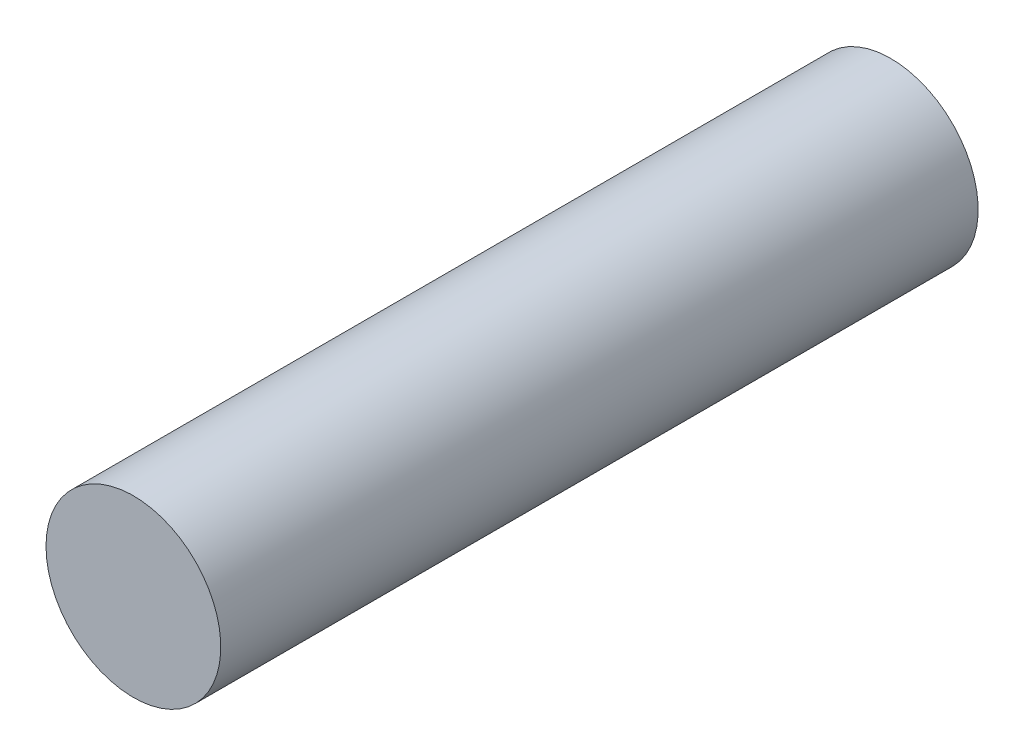
SolidWorks part; units mm, degrees
ref_plane "Front" through (0, 0, 0) normal (0, 0, 1) x (1, 0, 0)
ref_plane "Top" through (0, 0, 0) normal (0, 1, 0) x (1, 0, 0)
ref_plane "Right" through (0, 0, 0) normal (1, 0, 0) x (0, 0, -1)
sketch "Sketch1" plane through (0, 0, 0) normal (0, 0, 1) x (1, 0, 0)
  circle A0 centre (0, 0) radius 1.5
  dimension "D1" = 3
extrude "Boss-Extrude1" add sketch "Sketch1" along normal mid plane 13
